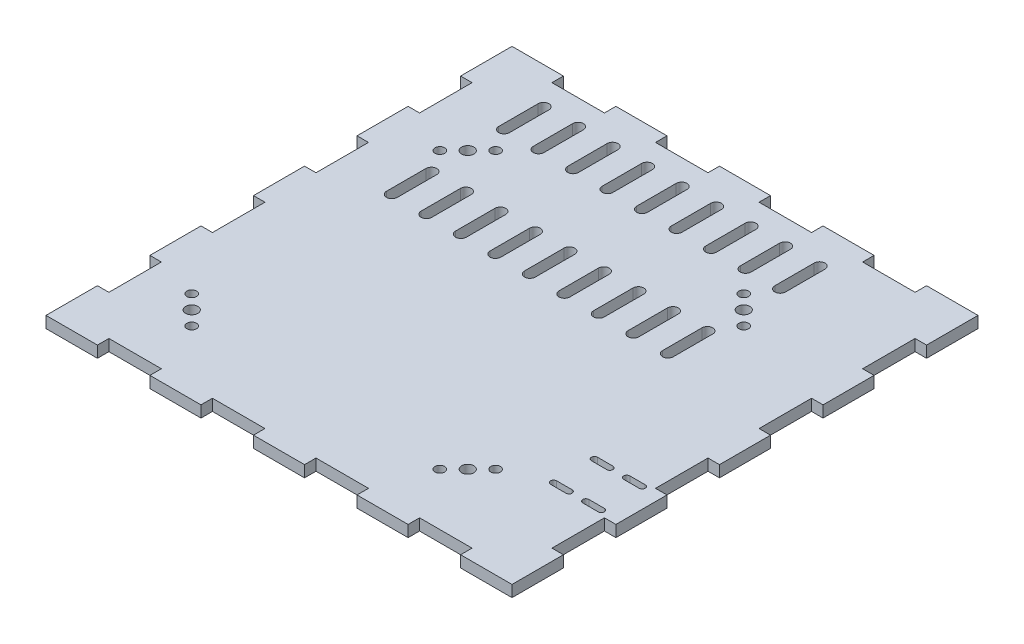
SolidWorks part; units mm, degrees
material "Acrylic (Medium-high impact)"
ref_plane "Front Plane" through (0, 0, 0) normal (0, 0, 1) x (1, 0, 0)
ref_plane "Top Plane" through (0, 0, 0) normal (0, 1, 0) x (1, 0, 0)
ref_plane "Right Plane" through (0, 0, 0) normal (1, 0, 0) x (0, 0, -1)
sketch "Board refrence" plane through (0, 0, 0) normal (0, 1, 0) x (1, 0, 0)
  line L0 (45, -19.76) -> (50, -19.76)
  line L1 (-42.5, -42.5) -> (42.5, -42.5)
  line L2 (-42.5, -42.5) -> (-42.5, 42.5)
  line L3 (-42.5, 42.5) -> (42.5, 42.5)
  line L4 (42.5, -42.5) -> (42.5, 42.5)
  line L5 (-42.5, -42.5) -> (42.5, 42.5) construction
  line L6 (-42.5, 42.5) -> (42.5, -42.5) construction
  line L7 (-50.8, 48.85) -> (50.8, 48.85)
  line L8 (-50.8, 48.85) -> (-50.8, 42.5)
  line L9 (-50.8, 42.5) -> (50.8, 42.5)
  line L10 (50.8, 48.85) -> (50.8, 42.5)
  line L11 (45, -27.76) -> (50, -27.76)
  line L12 (47.5, -27.76) -> (47.5, -19.76) construction
  circle A0 centre (-38.5, 38.5) radius 1.6
  circle A1 centre (-38.5, -38.5) radius 1.6
  circle A2 centre (38.5, -38.5) radius 1.6
  circle A3 centre (38.5, 38.5) radius 1.6
  point P0 (0, 0)
  point P14 (0, 42.5)
  point P15 (0, 42.5)
  point P26 (47.5, -23.76)
  dimension "D4" = 3.2
  dimension "D1" = 85
  dimension "D2" = 85
  dimension "D3" = 4
  dimension "D5" = 6.35
  dimension "D6" = 101.6
  dimension "D7" = 18.74
  dimension "D8" = 8
  dimension "D9" = 5
  dimension "D10" = 5
sketch "Sketch2" plane through (0, 0, 0) normal (0, 1, 0) x (1, 0, 0)
  line L0 (-42.5, -42.5) -> (-42.5, 42.5) construction
  line L1 (-54.3, 66.65) -> (69.3, 66.65) construction
  line L2 (-54.3, 66.65) -> (-54.3, -56.95) construction
  line L3 (-54.3, -56.95) -> (69.3, -56.95) construction
  line L4 (69.3, 66.65) -> (69.3, -56.95) construction
  line L6 (42.5, -42.5) -> (42.5, 42.5) construction
  line L7 (-50.8, 48.85) -> (50.8, 48.85) construction
  line L8 (-57.5, 69.85) -> (-57.5, -60.15)
  line L9 (-57.5, -60.15) -> (72.5, -60.15)
  line L10 (72.5, 69.85) -> (72.5, -60.15)
  line L11 (-57.5, 69.85) -> (72.5, 69.85)
  circle A0 centre (-38.5, 38.5) radius 1.7
  circle A1 centre (-38.5, -38.5) radius 1.7
  circle A2 centre (38.5, -38.5) radius 1.7
  circle A3 centre (38.5, 38.5) radius 1.7
  point P16 (0, 0)
  dimension "D1" = 3.4
  dimension "D2" = 15
  dimension "D3" = 21
  dimension "D4" = 30
  dimension "D6" = 130
  dimension "D5" = 3.2
extrude "Boss-Extrude1" add sketch "Sketch2" along normal blind 3.2
sketch "Sketch5" plane through (0, 3.2, 0) normal (0, 1, 0) x (1, 0, 0)
  line L0 (34.6109, 42.3891) -> (42.3891, 34.6109) construction
  line L1 (72.5, -60.15) -> (72.5, 69.85) construction
  circle A0 centre (42.3891, 34.6109) radius 1.35
  circle A1 centre (34.6109, 42.3891) radius 1.35
  circle A2 centre (34.6109, -42.3891) radius 1.35
  circle A3 centre (42.3891, -34.6109) radius 1.35
  circle A4 centre (-42.3891, -34.6109) radius 1.35
  circle A5 centre (-34.6109, -42.3891) radius 1.35
  circle A6 centre (-34.6109, 42.3891) radius 1.35
  circle A7 centre (-42.3891, 34.6109) radius 1.35
  point P4 (38.5, 38.5)
  point P23 (0, 0)
  dimension "D3" = 2.7
  dimension "D1" = 45
  dimension "D2" = 11
extrude "Cut-Extrude2" cut sketch "Sketch5" against normal up to next
sketch "Sketch4" plane through (0, 3.2, 0) normal (0, 1, 0) x (1, 0, 0)
  line L0 (72.5, 55.4056) -> (72.5, 40.9611)
  line L1 (72.5, -60.15) -> (72.5, 69.85) construction
  line L2 (72.5, 12.0722) -> (69.3, 12.0722)
  line L3 (69.3, 12.0722) -> (69.3, 26.5167)
  line L4 (69.3, 26.5167) -> (72.5, 26.5167)
  line L5 (72.5, 26.5167) -> (72.5, 12.0722)
  line L6 (72.5, -16.8167) -> (69.3, -16.8167)
  line L7 (69.3, -16.8167) -> (69.3, -2.3722)
  line L8 (69.3, -2.3722) -> (72.5, -2.3722)
  line L9 (72.5, -2.3722) -> (72.5, -16.8167)
  line L10 (72.5, 40.9611) -> (69.3, 40.9611)
  line L11 (69.3, 40.9611) -> (69.3, 55.4056)
  line L12 (69.3, 55.4056) -> (72.5, 55.4056)
  line L13 (72.5, -45.7056) -> (69.3, -45.7056)
  line L14 (69.3, -45.7056) -> (69.3, -31.2611)
  line L15 (69.3, -31.2611) -> (72.5, -31.2611)
  line L16 (72.5, -31.2611) -> (72.5, -45.7056)
  line L17 (72.5, 40.9611) -> (72.5, 12.0722) construction
  line L18 (69.3, -45.7056) -> (69.3, -60.15) construction
  line L19 (-57.5, -60.15) -> (72.5, -60.15) construction
  line L20 (69.3, -31.2611) -> (69.3, -16.8167) construction
  line L21 (72.5, 69.85) -> (-57.5, 69.85) construction
  line L42 (-57.5, 69.85) -> (72.5, -60.15) construction
  line L66 (-43.0556, -60.15) -> (-43.0556, -56.95)
  line L67 (-43.0556, -56.95) -> (-28.6111, -56.95)
  line L68 (-28.6111, -56.95) -> (-28.6111, -60.15)
  line L91 (69.3, -2.3722) -> (69.3, 12.0722) construction
  line L92 (69.3, 26.5167) -> (69.3, 40.9611) construction
  line L93 (69.3, 55.4056) -> (69.3, 69.85) construction
  line L94 (-28.6111, -60.15) -> (-43.0556, -60.15)
  line L95 (-14.1667, -60.15) -> (-14.1667, -56.95)
  line L96 (-14.1667, -56.95) -> (0.2778, -56.95)
  line L97 (0.2778, -56.95) -> (0.2778, -60.15)
  line L103 (0.2778, -60.15) -> (-14.1667, -60.15)
  line L108 (14.7222, -60.15) -> (14.7222, -56.95)
  line L113 (14.7222, -56.95) -> (29.1667, -56.95)
  line L118 (29.1667, -56.95) -> (29.1667, -60.15)
  line L119 (29.1667, -60.15) -> (14.7222, -60.15)
  line L120 (58.0556, -60.15) -> (43.6111, -60.15)
  line L121 (43.6111, -60.15) -> (43.6111, -56.95)
  line L125 (43.6111, -56.95) -> (58.0556, -56.95)
  line L126 (58.0556, -56.95) -> (58.0556, -60.15)
  line L127 (-57.5, 55.4056) -> (-54.3, 55.4056)
  line L128 (-54.3, 55.4056) -> (-54.3, 40.9611)
  line L129 (-54.3, 40.9611) -> (-57.5, 40.9611)
  line L130 (-57.5, 40.9611) -> (-57.5, 55.4056)
  line L131 (-57.5, 26.5167) -> (-54.3, 26.5167)
  line L132 (-54.3, 26.5167) -> (-54.3, 12.0722)
  line L133 (-54.3, 12.0722) -> (-57.5, 12.0722)
  line L134 (-57.5, 12.0722) -> (-57.5, 26.5167)
  line L135 (-57.5, -2.3722) -> (-54.3, -2.3722)
  line L136 (-54.3, -2.3722) -> (-54.3, -16.8167)
  line L137 (-54.3, -16.8167) -> (-57.5, -16.8167)
  line L138 (-57.5, -16.8167) -> (-57.5, -2.3722)
  line L139 (-57.5, -45.7056) -> (-57.5, -31.2611)
  line L140 (-57.5, -31.2611) -> (-54.3, -31.2611)
  line L141 (-54.3, -31.2611) -> (-54.3, -45.7056)
  line L142 (-54.3, -45.7056) -> (-57.5, -45.7056)
  line L143 (58.0556, 69.85) -> (58.0556, 66.65)
  line L144 (58.0556, 66.65) -> (43.6111, 66.65)
  line L145 (43.6111, 66.65) -> (43.6111, 69.85)
  line L146 (43.6111, 69.85) -> (58.0556, 69.85)
  line L147 (29.1667, 69.85) -> (29.1667, 66.65)
  line L148 (29.1667, 66.65) -> (14.7222, 66.65)
  line L149 (14.7222, 66.65) -> (14.7222, 69.85)
  line L150 (14.7222, 69.85) -> (29.1667, 69.85)
  line L151 (0.2778, 69.85) -> (0.2778, 66.65)
  line L152 (0.2778, 66.65) -> (-14.1667, 66.65)
  line L153 (-14.1667, 66.65) -> (-14.1667, 69.85)
  line L154 (-14.1667, 69.85) -> (0.2778, 69.85)
  line L155 (-43.0556, 69.85) -> (-28.6111, 69.85)
  line L156 (-28.6111, 69.85) -> (-28.6111, 66.65)
  line L157 (-28.6111, 66.65) -> (-43.0556, 66.65)
  line L158 (-43.0556, 66.65) -> (-43.0556, 69.85)
  point P27 (7.5, 4.85)
  point P81 (7.5, 4.85)
  dimension "D4" = 3.2
  dimension "D1" = 4
  dimension "D2" = 4
extrude "Cut-Extrude1" cut sketch "Sketch4" against normal through all
sketch "Pad reference" plane through (0, 3.2, 0) normal (0, 1, 0) x (1, 0, 0)
  line L151 (72.5, -60.15) -> (72.5, -45.7056) construction
  line L152 (72.5, 69.85) -> (58.0556, 69.85) construction
  line L153 (-50.5, -53.15) -> (-43.0556, -53.15)
  line L154 (-50.5, -45.7056) -> (-50.5, -53.15)
  line L155 (-50.5, -53.15) -> (-43.0556, -53.15) construction
  line L156 (-50.5, -45.7056) -> (-50.5, -53.15) construction
  circle A0 centre (-50.5, 62.85) radius 4
  circle A1 centre (65.5, 62.85) radius 4
  circle A2 centre (65.5, -53.15) radius 4
  circle A3 centre (-50.5, -53.15) radius 4
  dimension "D1" = 8
  dimension "D3" = 7
  dimension "D4" = 7
  dimension "D2" = 7
sketch "Sketch6" plane through (0, 3.2, 0) normal (0, 1, 0) x (1, 0, 0)
  line L0 (67, -29.7389) -> (62.7, -29.7389) construction
  line L1 (67, -30.5889) -> (62.7, -30.5889)
  line L2 (67, -28.8889) -> (62.7, -28.8889)
  line L3 (58, -29.7389) -> (53.7, -29.7389) construction
  line L4 (58, -30.5889) -> (53.7, -30.5889)
  line L5 (58, -28.8889) -> (53.7, -28.8889)
  line L6 (72.5, -24.0389) -> (-49927.5, -24.0389) construction
  line L7 (72.5, -31.2611) -> (72.5, -16.8167) construction
  line L8 (58, -18.3389) -> (53.7, -18.3389) construction
  line L9 (58, -17.4889) -> (53.7, -17.4889)
  line L10 (58, -19.1889) -> (53.7, -19.1889)
  line L11 (67, -18.3389) -> (62.7, -18.3389) construction
  line L12 (67, -17.4889) -> (62.7, -17.4889)
  line L13 (67, -19.1889) -> (62.7, -19.1889)
  arc A0 (67, -30.5889) -> (67, -28.8889) centre (67, -29.7389) ccw
  arc A1 (62.7, -28.8889) -> (62.7, -30.5889) centre (62.7, -29.7389) ccw
  arc A2 (58, -30.5889) -> (58, -28.8889) centre (58, -29.7389) ccw
  arc A3 (53.7, -28.8889) -> (53.7, -30.5889) centre (53.7, -29.7389) ccw
  arc A4 (58, -17.4889) -> (58, -19.1889) centre (58, -18.3389) cw
  arc A5 (53.7, -19.1889) -> (53.7, -17.4889) centre (53.7, -18.3389) cw
  arc A6 (67, -17.4889) -> (67, -19.1889) centre (67, -18.3389) cw
  arc A7 (62.7, -19.1889) -> (62.7, -17.4889) centre (62.7, -18.3389) cw
  point P2 (64.85, -29.7389)
  point P7 (55.85, -29.7389)
  point P18 (72.5, -24.0389)
  point P21 (55.85, -18.3389)
  point P28 (64.85, -18.3389)
  dimension "D3" = 3
  dimension "D1" = 4.3
  dimension "D2" = 1.7
  dimension "D4" = 4.85
  dimension "D5" = 5.5
extrude "Cut-Extrude3" cut sketch "Sketch6" against normal up to next
sketch "Sketch7" plane through (0, 3.2, 0) normal (0, 1, 0) x (1, 0, 0)
  line L0 (-38.5, 59.65) -> (-38.5, 48.65) construction
  line L1 (-37, 59.65) -> (-37, 48.65)
  line L2 (-40, 59.65) -> (-40, 48.65)
  line L3 (-43.0556, 66.65) -> (-28.6111, 66.65) construction
  line L5 (-30.375, 59.65) -> (-30.375, 48.65)
  line L6 (-27.375, 59.65) -> (-27.375, 48.65)
  line L7 (-28.875, 59.65) -> (-28.875, 48.65) construction
  line L8 (-20.75, 59.65) -> (-20.75, 48.65)
  line L9 (-17.75, 59.65) -> (-17.75, 48.65)
  line L10 (-19.25, 59.65) -> (-19.25, 48.65) construction
  line L11 (-11.125, 59.65) -> (-11.125, 48.65)
  line L12 (-8.125, 59.65) -> (-8.125, 48.65)
  line L13 (-9.625, 59.65) -> (-9.625, 48.65) construction
  line L14 (-1.5, 59.65) -> (-1.5, 48.65)
  line L15 (1.5, 59.65) -> (1.5, 48.65)
  line L16 (0, 59.65) -> (0, 48.65) construction
  line L17 (8.125, 59.65) -> (8.125, 48.65)
  line L18 (11.125, 59.65) -> (11.125, 48.65)
  line L19 (9.625, 59.65) -> (9.625, 48.65) construction
  line L20 (17.75, 59.65) -> (17.75, 48.65)
  line L21 (20.75, 59.65) -> (20.75, 48.65)
  line L22 (19.25, 59.65) -> (19.25, 48.65) construction
  line L23 (27.375, 59.65) -> (27.375, 48.65)
  line L24 (30.375, 59.65) -> (30.375, 48.65)
  line L25 (28.875, 59.65) -> (28.875, 48.65) construction
  line L26 (37, 59.65) -> (37, 48.65)
  line L27 (40, 59.65) -> (40, 48.65)
  line L28 (38.5, 59.65) -> (38.5, 48.65) construction
  line L31 (-40, 28.35) -> (-40, 17.35)
  line L32 (-38.5, 38.5) -> (-38.5, 48.65) construction
  line L33 (-38.5, 38.5) -> (-38.5, 28.35) construction
  line L35 (-37, 28.35) -> (-37, 17.35)
  line L36 (-38.5, 28.35) -> (-38.5, 17.35) construction
  line L37 (-30.375, 28.35) -> (-30.375, 17.35)
  line L38 (-27.375, 28.35) -> (-27.375, 17.35)
  line L39 (-28.875, 28.35) -> (-28.875, 17.35) construction
  line L40 (-20.75, 28.35) -> (-20.75, 17.35)
  line L41 (-17.75, 28.35) -> (-17.75, 17.35)
  line L42 (-19.25, 28.35) -> (-19.25, 17.35) construction
  line L43 (-11.125, 28.35) -> (-11.125, 17.35)
  line L44 (-8.125, 28.35) -> (-8.125, 17.35)
  line L45 (-9.625, 28.35) -> (-9.625, 17.35) construction
  line L46 (-1.5, 28.35) -> (-1.5, 17.35)
  line L47 (1.5, 28.35) -> (1.5, 17.35)
  line L48 (0, 28.35) -> (0, 17.35) construction
  line L49 (8.125, 28.35) -> (8.125, 17.35)
  line L50 (11.125, 28.35) -> (11.125, 17.35)
  line L51 (9.625, 28.35) -> (9.625, 17.35) construction
  line L52 (17.75, 28.35) -> (17.75, 17.35)
  line L53 (20.75, 28.35) -> (20.75, 17.35)
  line L54 (19.25, 28.35) -> (19.25, 17.35) construction
  line L55 (27.375, 28.35) -> (27.375, 17.35)
  line L56 (30.375, 28.35) -> (30.375, 17.35)
  line L57 (28.875, 28.35) -> (28.875, 17.35) construction
  line L58 (37, 28.35) -> (37, 17.35)
  line L59 (40, 28.35) -> (40, 17.35)
  line L60 (38.5, 28.35) -> (38.5, 17.35) construction
  line L61 (38.5, 28.35) -> (38.5, 38.5) construction
  line L62 (38.5, 38.5) -> (38.5, 48.65) construction
  arc A0 (-37, 59.65) -> (-40, 59.65) centre (-38.5, 59.65) ccw
  arc A1 (-40, 48.65) -> (-37, 48.65) centre (-38.5, 48.65) ccw
  arc A2 (-27.375, 59.65) -> (-30.375, 59.65) centre (-28.875, 59.65) ccw
  arc A3 (-30.375, 48.65) -> (-27.375, 48.65) centre (-28.875, 48.65) ccw
  arc A4 (-17.75, 59.65) -> (-20.75, 59.65) centre (-19.25, 59.65) ccw
  arc A5 (-20.75, 48.65) -> (-17.75, 48.65) centre (-19.25, 48.65) ccw
  arc A6 (-8.125, 59.65) -> (-11.125, 59.65) centre (-9.625, 59.65) ccw
  arc A7 (-11.125, 48.65) -> (-8.125, 48.65) centre (-9.625, 48.65) ccw
  arc A8 (1.5, 59.65) -> (-1.5, 59.65) centre (0, 59.65) ccw
  arc A9 (-1.5, 48.65) -> (1.5, 48.65) centre (0, 48.65) ccw
  arc A10 (11.125, 59.65) -> (8.125, 59.65) centre (9.625, 59.65) ccw
  arc A11 (8.125, 48.65) -> (11.125, 48.65) centre (9.625, 48.65) ccw
  arc A12 (20.75, 59.65) -> (17.75, 59.65) centre (19.25, 59.65) ccw
  arc A13 (17.75, 48.65) -> (20.75, 48.65) centre (19.25, 48.65) ccw
  arc A14 (30.375, 59.65) -> (27.375, 59.65) centre (28.875, 59.65) ccw
  arc A15 (27.375, 48.65) -> (30.375, 48.65) centre (28.875, 48.65) ccw
  arc A16 (40, 59.65) -> (37, 59.65) centre (38.5, 59.65) ccw
  arc A17 (37, 48.65) -> (40, 48.65) centre (38.5, 48.65) ccw
  arc A18 (-37, 28.35) -> (-40, 28.35) centre (-38.5, 28.35) ccw
  arc A19 (-40, 17.35) -> (-37, 17.35) centre (-38.5, 17.35) ccw
  arc A20 (-27.375, 28.35) -> (-30.375, 28.35) centre (-28.875, 28.35) ccw
  arc A21 (-30.375, 17.35) -> (-27.375, 17.35) centre (-28.875, 17.35) ccw
  arc A22 (-17.75, 28.35) -> (-20.75, 28.35) centre (-19.25, 28.35) ccw
  arc A23 (-20.75, 17.35) -> (-17.75, 17.35) centre (-19.25, 17.35) ccw
  arc A24 (-8.125, 28.35) -> (-11.125, 28.35) centre (-9.625, 28.35) ccw
  arc A25 (-11.125, 17.35) -> (-8.125, 17.35) centre (-9.625, 17.35) ccw
  arc A26 (1.5, 28.35) -> (-1.5, 28.35) centre (0, 28.35) ccw
  arc A27 (-1.5, 17.35) -> (1.5, 17.35) centre (0, 17.35) ccw
  arc A28 (11.125, 28.35) -> (8.125, 28.35) centre (9.625, 28.35) ccw
  arc A29 (8.125, 17.35) -> (11.125, 17.35) centre (9.625, 17.35) ccw
  arc A30 (20.75, 28.35) -> (17.75, 28.35) centre (19.25, 28.35) ccw
  arc A31 (17.75, 17.35) -> (20.75, 17.35) centre (19.25, 17.35) ccw
  arc A32 (30.375, 28.35) -> (27.375, 28.35) centre (28.875, 28.35) ccw
  arc A33 (27.375, 17.35) -> (30.375, 17.35) centre (28.875, 17.35) ccw
  arc A34 (40, 28.35) -> (37, 28.35) centre (38.5, 28.35) ccw
  arc A35 (37, 17.35) -> (40, 17.35) centre (38.5, 17.35) ccw
  point P2 (-38.5, 54.15)
  point P12 (-40, 54.15)
  point P16 (-28.875, 54.15)
  point P23 (-19.25, 54.15)
  point P30 (-9.625, 54.15)
  point P37 (0, 54.15)
  point P44 (9.625, 54.15)
  point P51 (19.25, 54.15)
  point P58 (28.875, 54.15)
  point P65 (38.5, 54.15)
  point P75 (-38.5, 22.85)
  point P86 (-28.875, 22.85)
  point P93 (-19.25, 22.85)
  point P100 (-9.625, 22.85)
  point P107 (0, 22.85)
  point P114 (9.625, 22.85)
  point P121 (19.25, 22.85)
  point P128 (28.875, 22.85)
  point P135 (38.5, 22.85)
  dimension "D1" = 7
  dimension "D2" = 11
  dimension "D4" = 3
  dimension "D5" = 9
  dimension "D6" = 2
extrude "Cut-Extrude4" cut sketch "Sketch7" against normal up to next
other "Tolerance" flip direction yes face at (43.6111, 1.6, -68.25) face at (14.7222, 1.6, -68.25) face at (-14.1667, 1.6, -68.25) face at (-43.0556, 1.6, -68.25) face at (29.1667, 1.6, -68.25) face at (58.0556, 1.6, -68.25) face at (0.2778, 1.6, -68.25) face at (-28.6111, 1.6, -68.25) face at (-55.9, 1.6, -40.9611) face at (-55.9, 1.6, -55.4056) face at (-55.9, 1.6, -12.0722) face at (-55.9, 1.6, -26.5167) face at (-55.9, 1.6, 2.3722) face at (-55.9, 1.6, 16.8167) face at (-55.9, 1.6, 45.7056) face at (-55.9, 1.6, 31.2611) face at (-28.6111, 1.6, 58.55) face at (-43.0556, 1.6, 58.55) face at (-14.1667, 1.6, 58.55) face at (0.2778, 1.6, 58.55) face at (14.7222, 1.6, 58.55) face at (29.1667, 1.6, 58.55) face at (58.0556, 1.6, 58.55) face at (43.6111, 1.6, 58.55) face at (70.9, 1.6, 31.2611) face at (70.9, 1.6, 45.7056) face at (70.9, 1.6, 16.8167) face at (70.9, 1.6, 2.3722) face at (70.9, 1.6, -12.0722) face at (70.9, 1.6, -26.5167) face at (70.9, 1.6, -55.4056) face at (70.9, 1.6, -40.9611) offset 0.1 parameters "D1"=0.1
equation "\"D5@Board refrence\" =  ( 1 / 4 )  * 1in"
equation "\"D6@Board refrence\" = 4in"
equation "\"slot_depth\"= 3.2mm"
equation "\"slot_width_tolerance\"= 0.1mm"
equation "\"D4@Sketch4\"=\"slot_depth\""
